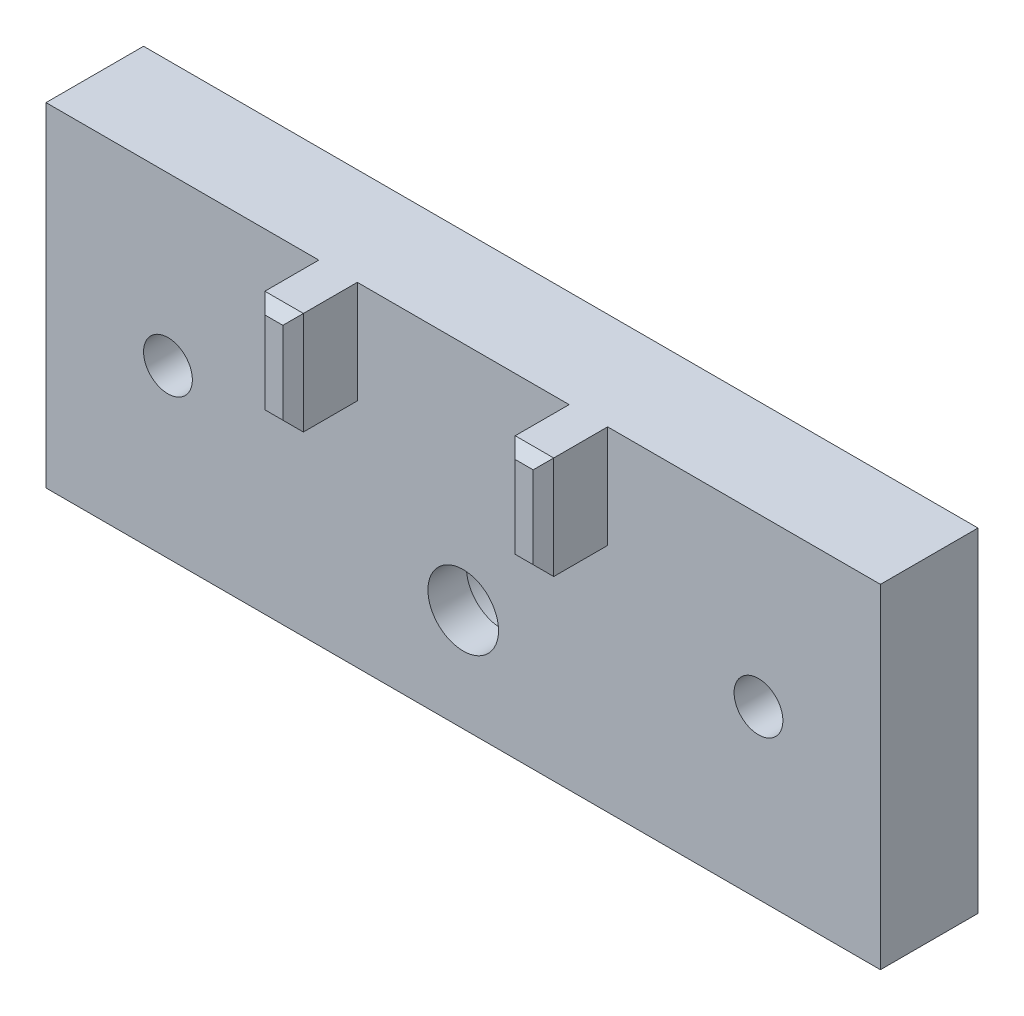
SolidWorks part; units mm, degrees
ref_plane "Top Plane" through (0, 0, 0) normal (0, 0, 1) x (1, 0, 0)
ref_plane "Front Plane" through (0, 0, 0) normal (0, 1, 0) x (1, 0, 0)
ref_plane "Right Plane" through (0, 0, 0) normal (1, 0, 0) x (0, 0, -1)
sketch "Sketch1" plane through (0, 0, 0) normal (0, 0, 1) x (1, 0, 0)
  line L1 (0, 0) -> (65, 0)
  line L2 (0, 0) -> (0, 26)
  line L3 (0, 26) -> (65, 26)
  line L4 (65, 0) -> (65, 26)
  dimension "D1" = 65
  dimension "D2" = 26
extrude "Boss-Extrude1" add sketch "Sketch1" along normal blind 8
sketch "Sketch2" plane through (0, 0, 8) normal (0, 0, 1) x (1, 0, 0)
  line L0 (0, 26) -> (0, 0) construction
  line L1 (0, 0) -> (65, 0) construction
  circle A0 centre (32.5, 8) radius 2.75
  dimension "D1" = 5.5
  dimension "D3" = 8
  dimension "D2" = 32.5
extrude "Cut-Extrude1" cut sketch "Sketch2" against normal blind 5
sketch "Sketch3" plane through (0, 0, 8) normal (0, 0, 1) x (1, 0, 0)
  line L0 (65, 26) -> (0, 26) construction
  line L1 (21.25, 26) -> (24.25, 26)
  line L2 (21.25, 26) -> (21.25, 18)
  line L3 (21.25, 18) -> (24.25, 18)
  line L4 (24.25, 26) -> (24.25, 18)
  line L6 (40.75, 26) -> (43.75, 26)
  line L7 (40.75, 26) -> (40.75, 18)
  line L8 (40.75, 18) -> (43.75, 18)
  line L9 (43.75, 26) -> (43.75, 18)
  circle A0 centre (32.5, 8) radius 2.75 construction
  dimension "D1" = 10
  dimension "D2" = 22.5
  dimension "D3" = 3
  dimension "D4" = 11.25
extrude "Boss-Extrude2" add sketch "Sketch3" along normal blind 5
chamfer "Chamfer1" distance 0.8 angle 45 8 edges at (42.25, 26, 13) (43.75, 22, 13) (42.25, 18, 13) (40.75, 22, 13) (22.75, 26, 13) (24.25, 22, 13) (22.75, 18, 13) (21.25, 22, 13)
sketch "Sketch4" plane through (0, 0, 0) normal (0, 0, -1) x (-1, 0, 0)
  line L1 (0, 0) -> (-65, 0) construction
  line L2 (-65, 0) -> (-65, 26) construction
  circle A0 centre (-55.5, 13) radius 1.9
  circle A1 centre (-9.5, 13) radius 1.9
  dimension "D2" = 13
  dimension "D3" = 9.5
  dimension "D4" = 3.8
  dimension "D1" = 46
extrude "Cut-Extrude2" cut sketch "Sketch4" against normal blind 8
sketch "Sketch5" plane through (0, 0, 0) normal (0, 0, -1) x (-1, 0, 0)
  line L2 (0, 26) -> (0, 0) construction
  line L3 (0, 0) -> (-65, 0) construction
  circle A0 centre (-32.5, 8) radius 4.5
  dimension "D1" = 9
  dimension "D3" = 8
  dimension "D2" = 32.5
extrude "Cut-Extrude3" cut sketch "Sketch5" against normal blind 5
chamfer "Chamfer2" distance 0.4 angle 45 7 edges at (32.5, 0, 0) (65, 13, 0) (32.5, 26, 0) (0, 13, 0) (7.6, 13, 0) (53.6, 13, 0) (28, 8, 0)
